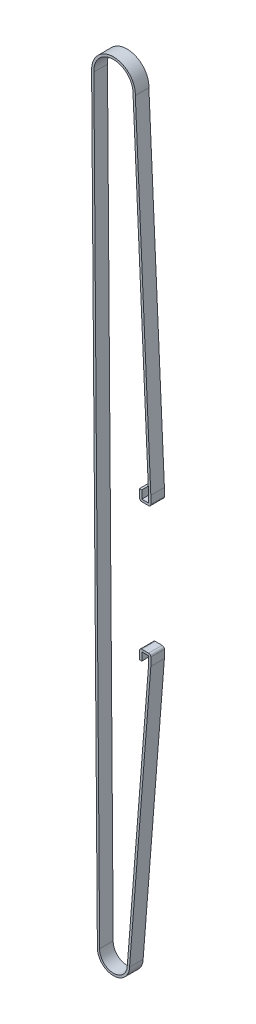
SolidWorks part; units mm, degrees
ref_plane "Front Plane" through (0, 0, 0) normal (0, 0, 1) x (1, 0, 0)
ref_plane "Top Plane" through (0, 0, 0) normal (0, 1, 0) x (1, 0, 0)
ref_plane "Right Plane" through (0, 0, 0) normal (1, 0, 0) x (0, 0, -1)
sketch "Sketch2" plane through (58.0839, 121.432, 69.5187) normal (0, 0, 1) x (0.9993, -0.0368, 0)
  line L0 (6.214, -334.485) -> (-8.6587, 0)
  line L2 (-9.66, 0) -> (5.2127, -334.485)
  line L4 (18.4314, -334.485) -> (23.4127, -214.4954)
  line L5 (23.4127, -214.4954) -> (23.282, -210.9478)
  line L6 (23.282, -210.9478) -> (20.284, -211.0582)
  line L7 (20.3043, -211.6079) -> (18.1137, -152.1482) construction
  line L8 (20.284, -211.0582) -> (23.282, -210.9478) construction
  line L9 (20.284, -211.0582) -> (20.4147, -214.6058)
  line L10 (20.4147, -214.6058) -> (19.4147, -214.6427)
  line L11 (19.4147, -214.6427) -> (19.2472, -210.0957)
  line L12 (19.2472, -210.0957) -> (24.2445, -209.9116)
  line L13 (24.2445, -209.9116) -> (24.412, -214.4586)
  line L14 (24.412, -214.4586) -> (19.4327, -334.485)
  line L15 (8.6587, 0) -> (21.0012, -149.0398)
  line L16 (21.0012, -149.0398) -> (21.1319, -152.5874)
  line L17 (21.1319, -152.5874) -> (18.134, -152.6978)
  line L18 (18.134, -152.6978) -> (18.0033, -149.1502)
  line L19 (18.0033, -149.1502) -> (17.004, -149.187)
  line L20 (17.004, -149.187) -> (17.1715, -153.734)
  line L21 (17.1715, -153.734) -> (22.1681, -153.5499)
  line L22 (22.1681, -153.5499) -> (22.0029, -149.0676)
  line L23 (22.0029, -149.0676) -> (9.66, 0)
  arc A0 (8.6587, 0) -> (-8.6245, -0.7685) centre (0, 0) ccw
  arc A1 (9.66, 0) -> (-9.6219, -0.8574) centre (0, 0) ccw
  arc A2 (6.214, -334.485) -> (18.4314, -334.485) centre (12.3227, -334.485) ccw
  arc A3 (5.2127, -334.485) -> (19.4327, -334.485) centre (12.3227, -334.485) ccw
  point P44 (19.6698, -153.6419)
  dimension "D1" = 19.32
  dimension "D2" = 1
  dimension "D3" = 1
  dimension "D4" = 1
  dimension "D5" = 1
  dimension "D6" = 1
  dimension "D7" = 1
extrude "Boss-Extrude1" add sketch "Sketch2" along normal blind 3 and the other way blind 3 contours L2 A3 L14 L13 L12 L11 L10 L9 L6 L5 L4 A2 L0 A0 L15 L16 L17 L18 L19 L20 L21 L22 L23 A1 region at (57.846, -219.7372, 69.5187)
fillet "Fillet1" radius 1 4 edges at (69.5832, -89.2299, 69.5187) (74.5839, -89.2299, 69.5187) (69.5839, -32.8299, 69.5187) (74.5839, -32.8299, 69.5187)
